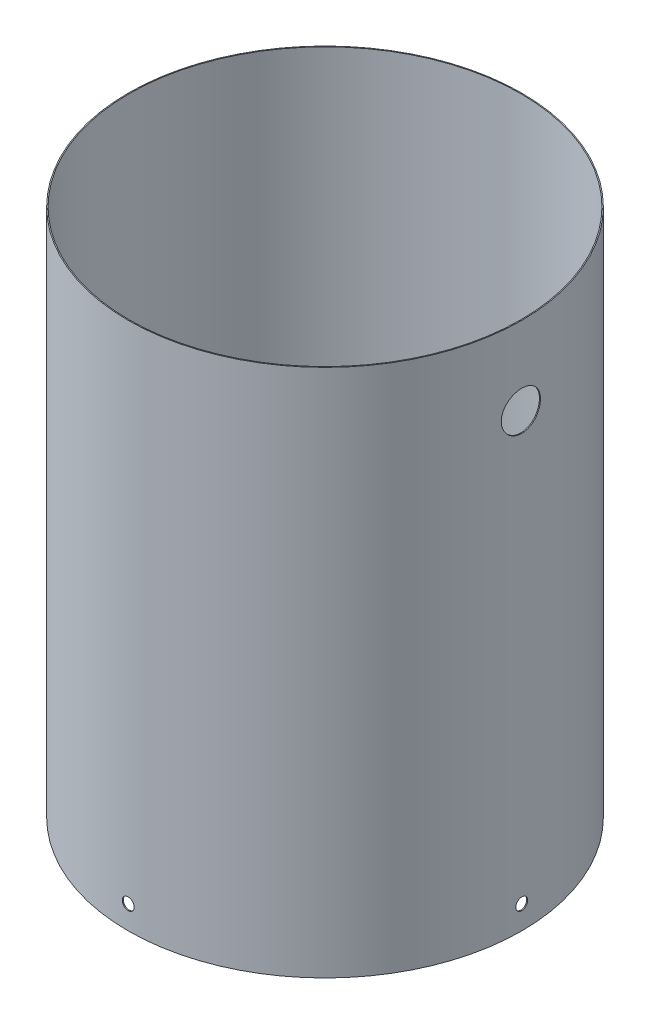
SolidWorks part; units mm, degrees
ref_plane "前视基准面" through (0, 0, 0) normal (0, 0, 1) x (1, 0, 0)
ref_plane "上视基准面" through (0, 0, 0) normal (0, 1, 0) x (1, 0, 0)
ref_plane "右视基准面" through (0, 0, 0) normal (1, 0, 0) x (0, 0, -1)
other "Configuration Table"
sketch "草图1" plane through (0, 0, 0) normal (0, 1, 0) x (1, 0, 0)
  circle A0 centre (0, 0) radius 100
  dimension "D1" = 200
extrude "拉伸-薄壁1" add sketch "草图1" along normal blind 270 thin thin type one direction wall 0.5
sketch "草图2" plane through (0, 0, 0) normal (0, 0, 1) x (1, 0, 0)
  line L0 (0, 0) -> (0, 61.2881) construction
  line L1 (49, 230) -> (147.6353, 230) construction
  line L2 (100, 270) -> (-100, 270) construction
  dimension "D1" = 40
ref_plane "基准面1" through (0, 0, 0) normal (1, 0, 0) x (0, 0, -1)
sketch "草图3" plane through (0, 0, 0) normal (1, 0, 0) x (0, 0, -1)
  line L0 (0, -200000) -> (0, 200061.2881) construction
  line L1 (100, 270) -> (-100, 270) construction
  line L2 (-100.5, 0) -> (100.5, 0) construction
  circle A0 centre (0, 230) radius 10
  circle A1 centre (0, 12) radius 3.02
  point P0 (0, 230)
  dimension "D2" = 20
  dimension "D3" = 6.04
  dimension "D5" = 218
  dimension "D1" = 40
  dimension "D4" = 12
extrude "切除-拉伸1" cut sketch "草图3" along normal through all both and the other way through all contours A1
extrude "切除-拉伸2" cut sketch "草图3<3>" along normal up to next contours A0
sketch "草图3<3>" plane through (0, 0, 0) normal (1, 0, 0) x (0, 0, -1) same geometry as "草图3"
sketch "草图6" plane through (0, 0, 0) normal (0, 0, 1) x (1, 0, 0)
  line L0 (0, -200000) -> (0, 200061.2881) construction
  line L1 (-100.5, 0) -> (100.5, 0) construction
  circle A0 centre (0, 12) radius 3.02
  dimension "D1" = 6.04
  dimension "D2" = 12
extrude "切除-拉伸3" cut sketch "草图6" against normal through all both and the other way through all
